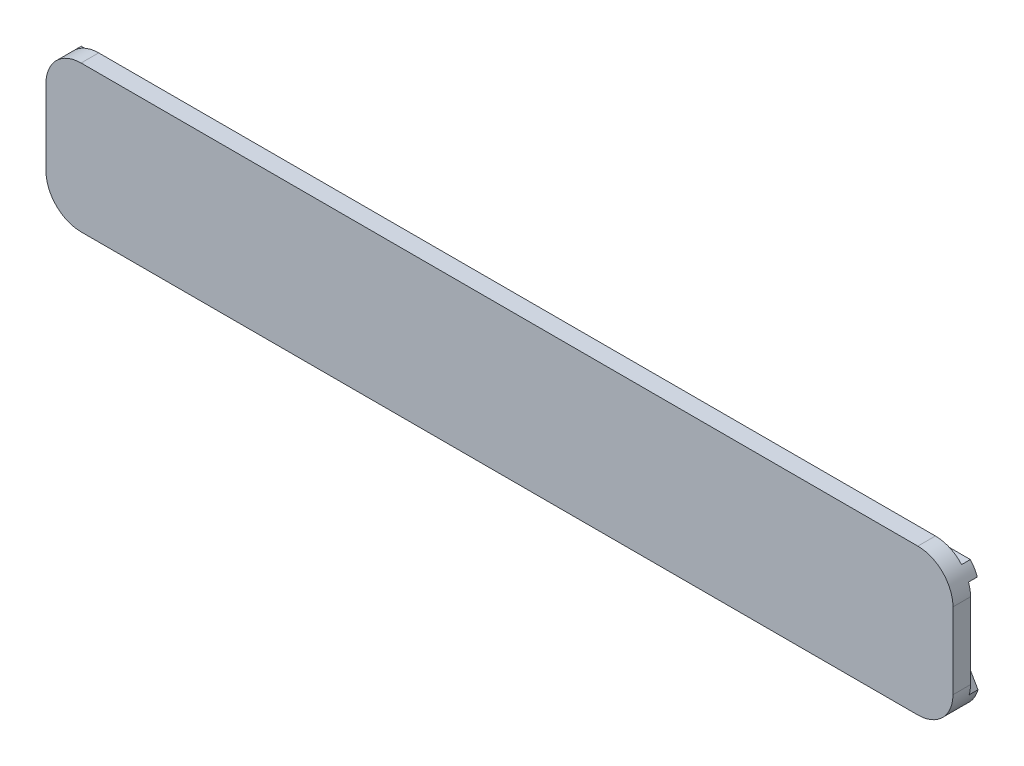
SolidWorks part; units mm, degrees
ref_plane "Front Plane" through (0, 0, 0) normal (0, 0, 1) x (1, 0, 0)
ref_plane "Top Plane" through (0, 0, 0) normal (0, 1, 0) x (1, 0, 0)
ref_plane "Right Plane" through (0, 0, 0) normal (1, 0, 0) x (0, 0, -1)
sketch "Sketch1" plane through (0, 0, 0) normal (0, 0, 1) x (1, 0, 0)
  line L0 (0, 0) -> (55.7, 0) construction
  line L1 (-49.65, 12.5) -> (105.35, 12.5)
  line L2 (-49.65, 12.5) -> (-49.65, -12.5)
  line L3 (-49.65, -12.5) -> (105.35, -12.5)
  line L4 (105.35, 12.5) -> (105.35, -12.5)
  circle A0 centre (55.7, 0) radius 3 construction
  circle A1 centre (0, 0) radius 3 construction
  circle A2 centre (55.7, 0) radius 3 construction
  circle A3 centre (0, 0) radius 3 construction
  circle A4 centre (0, 0) radius 3.3
  circle A5 centre (55.7, 0) radius 3.3
  point P14 (27.85, 0)
  point P15 (27.85, 12.5)
  point P16 (105.35, 0)
  dimension "D2" = 25
  dimension "D3" = 155
  dimension "D1" = 0.3
extrude "Boss-Extrude1" add sketch "Sketch1" against normal blind 2
sketch "Sketch2" plane through (0, 0, 0) normal (0, 0, 1) x (1, 0, 0)
  line L4 (-49.65, 12.5) -> (-49.65, -12.5)
  line L5 (-49.65, -12.5) -> (105.35, -12.5)
  line L6 (105.35, -12.5) -> (105.35, 12.5)
  line L7 (105.35, 12.5) -> (-49.65, 12.5)
  line L8 (-49.65, 12.5) -> (-49.65, -12.5)
  line L9 (-49.65, -12.5) -> (105.35, -12.5)
  line L10 (105.35, -12.5) -> (105.35, 12.5)
  line L11 (105.35, 12.5) -> (-49.65, 12.5)
  dimension "D1" = 0
extrude "Boss-Extrude2" add sketch "Sketch2" along normal blind 1
sketch "Sketch5" plane through (0, 0, -2) normal (0, 0, -1) x (-1, 0, 0)
  line L0 (-105.35, 0) -> (49894.65, 0) construction
  line L1 (-105.35, -12.5) -> (-105.35, 12.5) construction
  line L2 (49.65, 12.5) -> (49.65, -12.5) construction
  line L3 (-27.85, -10.5) -> (-27.85, -8.5)
  line L4 (-105.35, 10.5) -> (-27.85, 10.5)
  line L5 (-105.35, 10.5) -> (-105.35, 8.5)
  line L6 (-105.35, 8.5) -> (-95.535, 8.5)
  line L7 (-27.85, 10.5) -> (-27.85, 8.5)
  line L8 (-103.0406, -8.5) -> (-81.4107, -8.5)
  line L9 (-105.35, -10.5) -> (-105.35, -8.5)
  line L10 (-105.35, -10.5) -> (-27.85, -10.5)
  line L11 (-105.35, 12.5) -> (49.65, 12.5) construction
  line L12 (-105.35, -8.5) -> (-95.535, 8.5)
  line L13 (-93.2256, 8.5) -> (-91.2256, 8.5)
  line L14 (-88.9162, 8.5) -> (-79.1013, -8.5)
  line L15 (-79.1013, -8.5) -> (-77.1013, -8.5)
  line L16 (-74.7919, -8.5) -> (-64.9769, 8.5)
  line L17 (-103.0406, -8.5) -> (-93.2256, 8.5)
  line L18 (-93.2256, 8.5) -> (-91.2256, 8.5)
  line L19 (-91.2256, 8.5) -> (-81.4107, -8.5)
  line L20 (-77.1013, -8.5) -> (-67.2863, 8.5)
  line L21 (-40.9744, 8.5) -> (-31.1594, -8.5)
  line L23 (-28.85, -8.5) -> (-38.665, 8.5)
  line L25 (-93.2256, 8.5) -> (-91.2256, 8.5)
  line L26 (-88.9162, 8.5) -> (-67.2863, 8.5)
  line L27 (-79.1013, -8.5) -> (-77.1013, -8.5)
  line L28 (-74.7919, -8.5) -> (-49.6, -8.5)
  line L29 (-64.9769, 8.5) -> (-45.0449, 8.5)
  line L30 (-38.665, 8.5) -> (-27.85, 8.5)
  line L31 (-28.85, -8.5) -> (-27.85, -8.5)
  line L32 (-45.0449, 8.5) -> (-49.6, -8.5)
  line L34 (-47.5295, -8.5) -> (-42.9744, 8.5)
  line L35 (-42.9744, 8.5) -> (-40.9744, 8.5)
  line L36 (-47.5295, -8.5) -> (-31.1594, -8.5)
  point P4 (-105.35, 0)
  point P7 (49.65, 0)
  point P34 (-27.85, 12.5)
  line M32 (-105.35, 12.5) -> (-105.35, -12.5)
  dimension "D1" = 2
  dimension "D2" = 2
  dimension "D3" = 2
  dimension "D4" = 2
  dimension "D5" = 2
  dimension "D6" = 2
  dimension "D7" = 60
  dimension "D8" = 2
  dimension "D9" = 1
  dimension "D10" = 2
  dimension "D11" = 45
extrude "Boss-Extrude4" add sketch "Sketch5" along normal blind 1.5 contours L12 L0 L17 L13 L19 L14 L26 L20 L16 L29 L21 L23 L30 L7 L4 L6 M32 | L0 L12 L10 L3 L31 L23 L21 L28 L16 L20 L15 L14 L19 L8 L17 M32 region at (66.9728, 7.4905, -2) region at (99.2878, -0.7821, -2)
ref_plane "Plane1" through (27.85, 0, 0) normal (1, 0, 0) x (0, 0, -1)
mirror "Mirror1" about plane through (27.85, 0, 0) normal (1, 0, 0) of "Boss-Extrude4"
fillet "Fillet1" radius 6 4 edges at (105.35, 12.5, -0.5) (105.35, -12.5, -0.5) (-49.65, -12.5, -0.5) (-49.65, 12.5, -0.5)
sketch "Sketch3" plane through (0, 0, 1) normal (0, 0, 1) x (1, 0, 0)
  line L0 (-49.65, -5) -> (105.35, -5) construction
  line L1 (-43.65, -12.5) -> (99.35, -12.5) construction
  line L2 (-49.65, 6.5) -> (-49.65, -6.5) construction
  text T0 "ED Robotics" font "Century Gothic" height 10
  point P7 (27.85, -12.5)
  point P8 (27.85, -5)
  dimension "D1" = 5
extrude "Engraved team name" [suppressed] cut sketch "Sketch3" against normal blind 0.5
equation "\"D3@Sketch5\"=\"D1@Sketch5\""
equation "\"D4@Sketch5\"=\"D3@Sketch5\""
equation "\"D5@Sketch5\"=\"D3@Sketch5\""
equation "\"D6@Sketch5\"=\"D3@Sketch5\""
equation "\"D8@Sketch5\"=\"D3@Sketch5\""
equation "\"D9@Sketch5\"=\"D3@Sketch5\"/2"
equation "\"D10@Sketch5\"=\"D3@Sketch5\""
